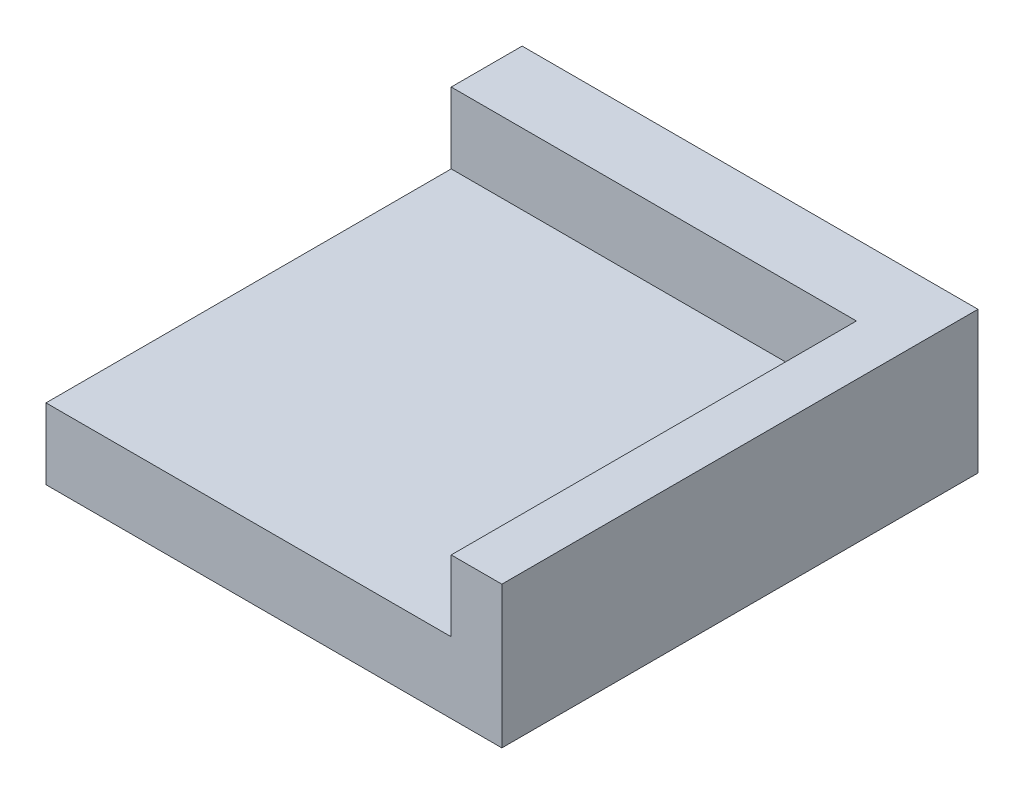
SolidWorks part; units mm, degrees
material "Pino"
ref_plane "Alzado" through (0, 0, 0) normal (0, 0, 1) x (1, 0, 0)
ref_plane "Planta" through (0, 0, 0) normal (0, 1, 0) x (1, 0, 0)
ref_plane "Vista lateral" through (0, 0, 0) normal (1, 0, 0) x (0, 0, -1)
sketch "Croquis3" plane through (0, 0, 0) normal (1, 0, 0) x (0, 0, -1)
  line L1 (-765.4161, 389.6671) -> (-530.4161, 389.6671)
  line L2 (-765.4161, 389.6671) -> (-765.4161, 354.6671)
  line L3 (-765.4161, 354.6671) -> (-530.4161, 354.6671)
  line L4 (-530.4161, 389.6671) -> (-530.4161, 354.6671)
  line L5 (-530.4161, 389.6671) -> (-565.4161, 389.6671)
  line L6 (-530.4161, 389.6671) -> (-530.4161, 424.6671)
  line L7 (-530.4161, 424.6671) -> (-565.4161, 424.6671)
  line L8 (-565.4161, 389.6671) -> (-565.4161, 424.6671)
  dimension "D1" = 235
  dimension "D2" = 35
  dimension "D3" = 35
  dimension "D4" = 35
extrude "Saliente-Extruir1" add sketch "Croquis3" along normal blind 225 contours L8 L1 L6 L7 | L4 L1 L2 L3 region at (0, 372.1671, 647.9161) region at (0, 407.1671, 547.9161)
sketch "Croquis4" plane through (0, 0, 565.4161) normal (0, 0, 1) x (1, 0, 0)
  line L0 (225, 389.6671) -> (0, 389.6671) construction
  line L1 (225, 424.6671) -> (200, 424.6671)
  line L2 (225, 424.6671) -> (225, 389.6671)
  line L3 (225, 389.6671) -> (200, 389.6671)
  line L4 (200, 424.6671) -> (200, 389.6671)
  dimension "D1" = 25
extrude "Saliente-Extruir2" add sketch "Croquis4" along normal blind 200
